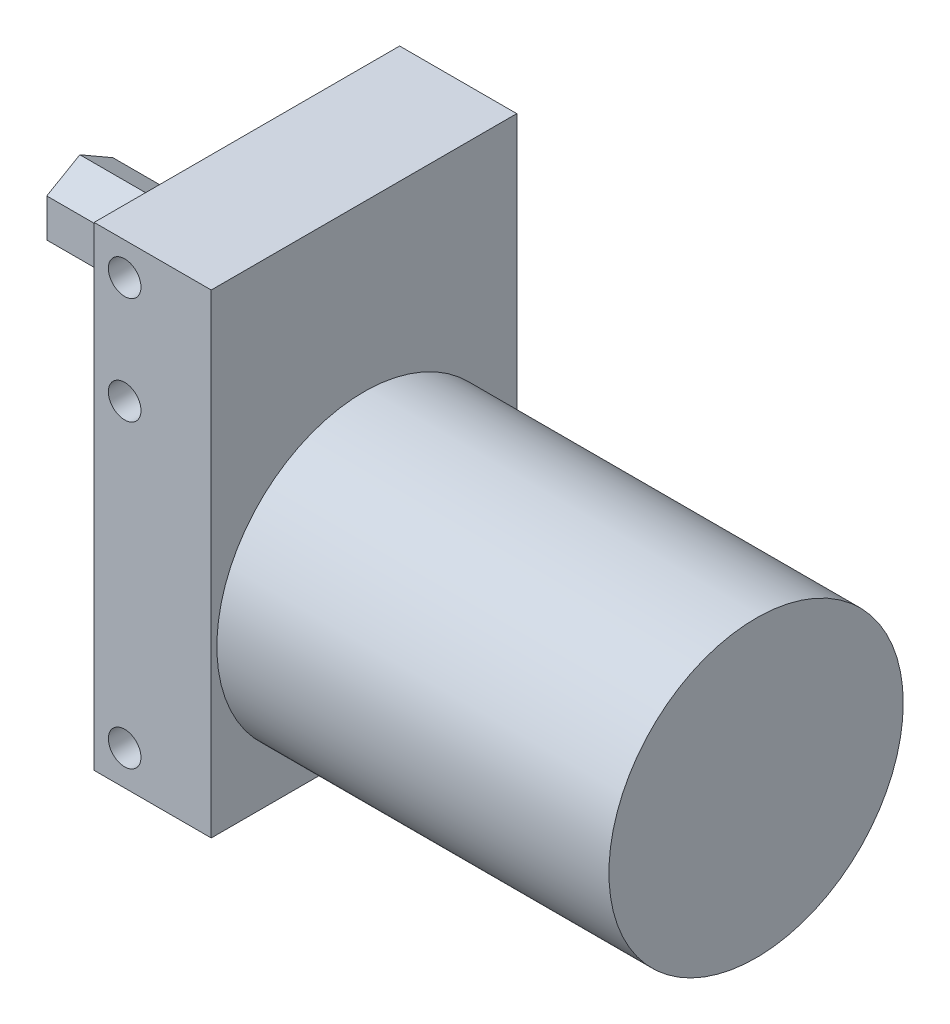
SolidWorks part; units mm, degrees
ref_plane "前视基准面" through (0, 0, 0) normal (0, 0, 1) x (1, 0, 0)
ref_plane "上视基准面" through (0, 0, 0) normal (0, 1, 0) x (1, 0, 0)
ref_plane "右视基准面" through (0, 0, 0) normal (1, 0, 0) x (0, 0, -1)
other "Configuration Table"
sketch "草图1" plane through (0, 0, 0) normal (1, 0, 0) x (0, 0, -1)
  line L0 (15, 0) -> (15, 53.9132) construction
  line L1 (0, 0) -> (30, 0)
  line L2 (0, 0) -> (0, 46.6)
  line L3 (0, 46.6) -> (30, 46.6)
  line L4 (30, 0) -> (30, 46.6)
  line L6 (18.25, 34.7764) -> (15, 36.6528)
  line L7 (15, 36.6528) -> (11.75, 34.7764)
  line L8 (11.75, 34.7764) -> (11.75, 31.0236)
  line L9 (11.75, 31.0236) -> (15, 29.1472)
  line L10 (15, 29.1472) -> (18.25, 31.0236)
  line L11 (18.25, 31.0236) -> (18.25, 34.7764)
  circle A0 centre (15, 32.9) radius 7
  circle A1 centre (15, 32.9) radius 3.25 construction
  circle A2 centre (15, 32.9) radius 1.6
  dimension "D3" = 13.7
  dimension "D4" = 14
  dimension "D6" = 3.2
  dimension "D1" = 46.6
  dimension "D2" = 30
  dimension "D5" = 6.5
extrude "凸台-拉伸1" add sketch "草图1" along normal blind 11.5 contours L1 L4 L3 L2 A0 | A0 L11 L10 L9 L8 L7 L6 | L10 L11 L6 L7 L8 L9 A2 | A2 region at (0, 22.1121, -15) region at (0, 32.9, -18.1507) region at (0, 32.9, -8.198) region at (0, 32.9, -15)
extrude "凸台-拉伸2" add sketch "草图1<3>" against normal blind 2.5 contours A0 L11 L10 L9 L8 L7 L6 region at (0, 32.9, -8.198)
sketch "草图1<3>" plane through (0, 0, 0) normal (1, 0, 0) x (0, 0, -1) same geometry as "草图1"
extrude "凸台-拉伸3" add sketch "草图1<4>" against normal blind 16.4 contours L10 L11 L6 L7 L8 L9 A2 region at (0, 32.9, -18.1507)
sketch "草图1<4>" plane through (0, 0, 0) normal (1, 0, 0) x (0, 0, -1) same geometry as "草图1"
extrude "凸台-拉伸4" add sketch "草图1<5>" against normal blind 10.4 contours A2 region at (0, 32.9, -15)
sketch "草图1<5>" plane through (0, 0, 0) normal (1, 0, 0) x (0, 0, -1) same geometry as "草图1"
sketch "草图2" plane through (11.5, 0, 0) normal (1, 0, 0) x (0, 0, -1)
  line L0 (15, 0) -> (15, 47.7301) construction
  line L1 (0, 0) -> (30, 0) construction
  circle A0 centre (15, 16) radius 14.45
  dimension "D1" = 28.9
  dimension "D2" = 16
extrude "凸台-拉伸5" add sketch "草图2" along normal blind 38.5
sketch "草图3" plane through (0, 0, 0) normal (0, 0, 1) x (1, 0, 0)
  line L0 (0, 0) -> (0, 46.6) construction
  line L1 (11.5, 46.6) -> (0, 46.6) construction
  circle A0 centre (3, 43.4) radius 1.6
  circle A1 centre (3, 32.9) radius 1.6
  circle A2 centre (3, 3.4) radius 1.6
  dimension "D1" = 3
  dimension "D2" = 3.2
  dimension "D3" = 10.5
  dimension "D4" = 3.2
  dimension "D5" = 40
extrude "切除-拉伸1" cut sketch "草图3" against normal blind 6
sketch "草图4" plane through (0, 0, -30) normal (0, 0, -1) x (-1, 0, 0)
  line L0 (0, 0) -> (0, 46.6) construction
  line L1 (-11.5, 46.6) -> (0, 46.6) construction
  circle A0 centre (-3.2, 43.4) radius 1.6
  circle A1 centre (-3.2, 32.9) radius 1.6
  circle A2 centre (-3.2, 3.4) radius 1.6
  dimension "D1" = 3.2
  dimension "D2" = 3.2
  dimension "D3" = 3.2
  dimension "D4" = 10.5
  dimension "D5" = 40
extrude "切除-拉伸2" cut sketch "草图4" against normal blind 3
